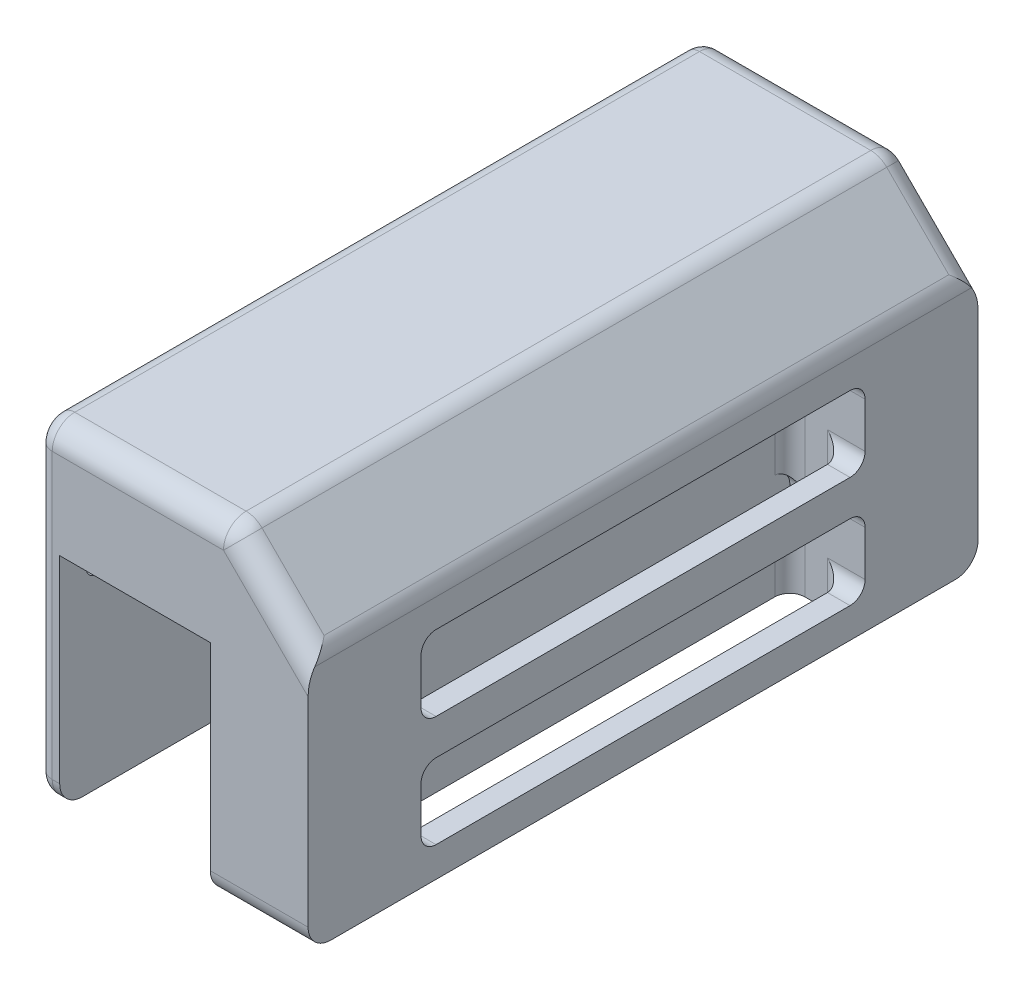
SolidWorks part; units mm, degrees
material "ABS"
ref_plane "Plano frontal" through (0, 0, 0) normal (0, 0, 1) x (1, 0, 0)
ref_plane "Plano superior" through (0, 0, 0) normal (0, 1, 0) x (1, 0, 0)
ref_plane "Plano direito" through (0, 0, 0) normal (1, 0, 0) x (0, 0, -1)
sketch "Esboço2" plane through (0, 0, 0) normal (1, 0, 0) x (0, 0, -1)
  line L1 (2.9016, -0.0625) -> (-35.0984, -0.0625) construction
  line L2 (2.9016, -0.0625) -> (-35.0984, -0.0625)
  line L6 (7.6893, -0.0625) -> (2.9016, -0.0625)
  line L8 (-39.8861, -0.0625) -> (-35.0984, -0.0625)
  line L9 (-60.5984, 9.4769) -> (-60.5984, 20.9769)
  line L10 (28.4016, 9.4769) -> (28.4016, 20.9769)
  line L11 (-57.5984, 23.9769) -> (25.4016, 23.9769)
  arc A0 (28.4016, 20.9769) -> (25.4016, 23.9769) centre (25.4016, 20.9769) ccw
  arc A1 (-60.5984, 20.9769) -> (-57.5984, 23.9769) centre (-57.5984, 20.9769) cw
  arc A2 (28.4016, 9.4769) -> (24.5016, 12.3387) centre (25.4016, 9.4769) ccw
  arc A3 (-48.8914, 5.5897) -> (-56.6984, 12.3387) centre (-60.5984, -0.0625) ccw
  arc A4 (-48.8914, 5.5897) -> (-39.8861, -0.0625) centre (-39.8861, 9.9375) ccw
  arc A5 (-60.5984, 9.4769) -> (-56.6984, 12.3387) centre (-57.5984, 9.4769) cw
  arc A6 (16.6946, 5.5897) -> (7.6893, -0.0625) centre (7.6893, 9.9375) cw
  arc A7 (16.6946, 5.5897) -> (24.5016, 12.3387) centre (28.4016, -0.0625) cw
  point P22 (28.4016, 12.9375)
  point P23 (-60.5984, 12.9375)
  dimension "D1" = 3
extrude "Ressalto-extrusão2" add sketch "Esboço2" along normal blind 30
sketch "Esboço3" plane through (0, 0, 0) normal (-1, 0, 0) x (0, 0, 1)
  line L0 (60.5984, 15.2269) -> (60.5984, 20.9769)
  line L1 (60.5984, 20.9769) -> (60.5984, 9.4769) construction
  line L2 (-28.4016, 15.2269) -> (-28.4016, 20.9769)
  line L3 (-28.4016, 9.4769) -> (-28.4016, 20.9769) construction
  line L4 (16.0984, 23.9769) -> (57.5984, 23.9769)
  line L5 (-25.4016, 23.9769) -> (57.5984, 23.9769) construction
  line L6 (16.0984, 23.9769) -> (-25.4016, 23.9769)
  line L7 (60.5984, 15.2269) -> (60.5984, -16.7731)
  line L8 (-28.4016, 15.2269) -> (-28.4016, -16.7731)
  line L9 (57.5984, -19.7731) -> (-25.4016, -19.7731)
  arc A0 (57.5984, 23.9769) -> (60.5984, 20.9769) centre (57.5984, 20.9769) cw
  arc A1 (-28.4016, 20.9769) -> (-25.4016, 23.9769) centre (-25.4016, 20.9769) cw
  arc A2 (-28.4016, -16.7731) -> (-25.4016, -19.7731) centre (-25.4016, -16.7731) ccw
  arc A3 (60.5984, -16.7731) -> (57.5984, -19.7731) centre (57.5984, -16.7731) cw
  dimension "D1" = 3
  dimension "D2" = 3
extrude "Ressalto-extrusão3" add sketch "Esboço3" along normal blind 3
sketch "Esboço4" plane through (30, 0, 0) normal (1, 0, 0) x (0, 0, -1)
  line L0 (-16.0984, 23.9769) -> (25.4016, 23.9769)
  line L1 (25.4016, 23.9769) -> (-57.5984, 23.9769) construction
  line L2 (-16.0984, 23.9769) -> (-57.5984, 23.9769)
  line L3 (28.4016, 15.2269) -> (28.4016, 20.9769)
  line L4 (28.4016, 9.4769) -> (28.4016, 20.9769) construction
  line L5 (-60.5984, 20.9769) -> (-60.5984, 15.2269)
  line L7 (28.4016, 15.2269) -> (28.4016, -16.7731)
  line L8 (28.4016, 9.4769) -> (28.4016, -16.7731) construction
  line L9 (-60.5984, 20.9769) -> (-60.5984, 9.4769) construction
  line L10 (-60.5984, 15.2269) -> (-60.5984, -16.7731)
  line L11 (25.4016, -19.7731) -> (-57.5984, -19.7731)
  arc A0 (25.4016, 23.9769) -> (28.4016, 20.9769) centre (25.4016, 20.9769) cw
  arc A1 (-60.5984, 20.9769) -> (-57.5984, 23.9769) centre (-57.5984, 20.9769) cw
  arc A2 (-60.5984, -16.7731) -> (-57.5984, -19.7731) centre (-57.5984, -16.7731) ccw
  arc A3 (28.4016, -16.7731) -> (25.4016, -19.7731) centre (25.4016, -16.7731) cw
  point P23 (28.4016, -19.7731)
  dimension "D1" = 3
extrude "Ressalto-extrusão4" add sketch "Esboço4" along normal blind 3 and the other way blind 10
sketch "Esboço8" plane through (33, 0, 0) normal (1, 0, 0) x (0, 0, -1)
  line L0 (-60.5984, 20.9769) -> (-60.5984, -16.7731) construction
  line L1 (-43.5984, 8.9769) -> (11.4016, 8.9769)
  line L2 (-45.5984, 6.9769) -> (-45.5984, 0.9769)
  line L3 (-43.5984, -1.0231) -> (11.4016, -1.0231)
  line L4 (13.4016, 6.9769) -> (13.4016, 0.9769)
  line L5 (28.4016, -16.7731) -> (28.4016, 20.9769) construction
  line L6 (25.4016, 23.9769) -> (-57.5984, 23.9769) construction
  line L7 (-57.5984, -19.7731) -> (25.4016, -19.7731) construction
  line L8 (-43.5984, -5.7731) -> (11.4016, -5.7731)
  line L9 (-45.5984, -7.7731) -> (-45.5984, -13.7731)
  line L10 (-43.5984, -15.7731) -> (11.4016, -15.7731)
  line L11 (13.4016, -7.7731) -> (13.4016, -13.7731)
  arc A0 (-43.5984, 8.9769) -> (-45.5984, 6.9769) centre (-43.5984, 6.9769) ccw
  arc A1 (-45.5984, 0.9769) -> (-43.5984, -1.0231) centre (-43.5984, 0.9769) ccw
  arc A2 (11.4016, 8.9769) -> (13.4016, 6.9769) centre (11.4016, 6.9769) cw
  arc A3 (11.4016, -1.0231) -> (13.4016, 0.9769) centre (11.4016, 0.9769) ccw
  arc A4 (11.4016, -5.7731) -> (13.4016, -7.7731) centre (11.4016, -7.7731) cw
  arc A5 (11.4016, -15.7731) -> (13.4016, -13.7731) centre (11.4016, -13.7731) ccw
  arc A6 (-45.5984, -13.7731) -> (-43.5984, -15.7731) centre (-43.5984, -13.7731) ccw
  arc A7 (-43.5984, -5.7731) -> (-45.5984, -7.7731) centre (-43.5984, -7.7731) ccw
  arc A8 (11.4016, -5.7731) -> (13.4016, -7.7731) centre (11.4016, -7.7731) cw
  point P22 (13.4016, 8.9769)
  point P25 (13.4016, -1.0231)
  point P28 (13.4016, -5.7731)
  point P31 (13.4016, -15.7731)
  dimension "D9" = 2
  dimension "D10" = 2
  dimension "D1" = 15
  dimension "D2" = 15
  dimension "D3" = 15
  dimension "D4" = 10
  dimension "D5" = 15
  dimension "D6" = 15
  dimension "D7" = 4
  dimension "D8" = 10
extrude "Corte-extrusão1" cut sketch "Esboço8" against normal blind 10 contours L8 A7 L9 A6 L10 A5 L11 A4 | L3 A3 L4 A2 L1 A0 L2 A1 region at (33, 3.9769, 16.0984) region at (33, -10.7731, 16.0984)
sketch "Esboço9" plane through (0, -19.7731, 0) normal (0, -1, 0) x (-1, 0, 0)
  line L0 (-20, 28.4016) -> (-33, 28.4016) construction
  line L1 (-25, 13.4016) -> (-28, 13.4016)
  line L2 (-23, 11.4016) -> (-23, -43.5984)
  line L3 (-25, -45.5984) -> (-28, -45.5984)
  line L4 (-30, 11.4016) -> (-30, -43.5984)
  line L5 (-20, -60.5984) -> (-33, -60.5984) construction
  line L6 (-33, -57.5984) -> (-33, 25.4016) construction
  line L7 (-20, -57.5984) -> (-20, 25.4016) construction
  arc A0 (-28, -45.5984) -> (-30, -43.5984) centre (-28, -43.5984) cw
  arc A1 (-23, -43.5984) -> (-25, -45.5984) centre (-25, -43.5984) cw
  arc A2 (-28, 13.4016) -> (-30, 11.4016) centre (-28, 11.4016) ccw
  arc A3 (-25, 13.4016) -> (-23, 11.4016) centre (-25, 11.4016) cw
  dimension "D5" = 2
  dimension "D1" = 15
  dimension "D2" = 15
  dimension "D3" = 3
  dimension "D4" = 3
extrude "Corte-extrusão2" cut sketch "Esboço9" against normal up to surface (28.75 mm away) up to face at (28, 8.9769, 16.0984)
sketch "Esboço10" plane through (0, 0, 0) normal (1, 0, 0) x (0, 0, -1)
  line L0 (-60.5984, -16.7731) -> (-60.5984, 9.4769) construction
  line L1 (28.4016, 9.4769) -> (28.4016, -16.7731) construction
  line L2 (-39.8861, -0.0625) -> (7.6893, -0.0625) construction
  circle A0 centre (-55.5984, 6.3387) radius 1.5
  circle A1 centre (23.4016, 6.3387) radius 1.5
  circle A2 centre (-16.0984, -8.5625) radius 1.5
  dimension "D1" = 3
  dimension "D2" = 3
  dimension "D3" = 3
  dimension "D4" = 5
  dimension "D5" = 6
  dimension "D6" = 5
  dimension "D7" = 6
  dimension "D8" = 8.5
  dimension "D9" = 44.5
extrude "Corte-extrusão3" cut sketch "Esboço10" against normal blind 10
sketch "Esboço12" plane through (0, 0, 0) normal (1, 0, 0) x (0, 0, -1)
  line L0 (28.4016, 9.4769) -> (28.4016, -16.7731) construction
  line L1 (-31.5984, -2.8625) -> (-25.5984, -2.8625)
  line L2 (-33.5984, -4.8625) -> (-33.5984, -14.7731)
  line L3 (-31.5984, -16.7731) -> (-25.5984, -16.7731)
  line L4 (-23.5984, -4.8625) -> (-23.5984, -14.7731)
  line L5 (-6.5984, -2.8625) -> (-0.5984, -2.8625)
  line L6 (-8.5984, -4.8625) -> (-8.5984, -14.7731)
  line L7 (-6.5984, -16.7731) -> (-0.5984, -16.7731)
  line L8 (1.4016, -4.8625) -> (1.4016, -14.7731)
  line L9 (-60.5984, -16.7731) -> (-60.5984, 9.4769) construction
  line L10 (25.4016, -19.7731) -> (-57.5984, -19.7731) construction
  line L11 (-39.8861, -0.0625) -> (7.6893, -0.0625) construction
  arc A0 (-0.5984, -2.8625) -> (1.4016, -4.8625) centre (-0.5984, -4.8625) cw
  arc A1 (-0.5984, -16.7731) -> (1.4016, -14.7731) centre (-0.5984, -14.7731) ccw
  arc A2 (-8.5984, -14.7731) -> (-6.5984, -16.7731) centre (-6.5984, -14.7731) ccw
  arc A3 (-6.5984, -2.8625) -> (-8.5984, -4.8625) centre (-6.5984, -4.8625) ccw
  arc A4 (-25.5984, -2.8625) -> (-23.5984, -4.8625) centre (-25.5984, -4.8625) cw
  arc A5 (-25.5984, -16.7731) -> (-23.5984, -14.7731) centre (-25.5984, -14.7731) ccw
  arc A6 (-31.5984, -2.8625) -> (-33.5984, -4.8625) centre (-31.5984, -4.8625) ccw
  arc A7 (-33.5984, -14.7731) -> (-31.5984, -16.7731) centre (-31.5984, -14.7731) ccw
  point P12 (-60.5984, -3.6481)
  point P21 (1.4016, -16.7731)
  point P24 (-8.5984, -16.7731)
  point P31 (-23.5984, -16.7731)
  point P36 (-33.5984, -16.7731)
  dimension "D9" = 2
  dimension "D1" = 52
  dimension "D2" = 52
  dimension "D3" = 3
  dimension "D4" = 3
  dimension "D5" = 2.8
  dimension "D6" = 2.8
  dimension "D7" = 10
  dimension "D8" = 10
extrude "Corte-extrusão4" cut sketch "Esboço12" against normal blind 10
fillet "Filete2" radius 2 8 edges at (-3, 23.0982, 59.7197) (-3, 2.1019, 60.5984) (-3, -18.8944, 59.7197) (-3, -19.7731, 16.0984) (-3, -18.8944, -27.5229) (-3, 2.1019, -28.4016) (-3, 23.0982, -27.5229) (-3, 23.9769, 16.0984)
sketch "Esboço13" plane through (-3, 0, 0) normal (-1, 0, 0) x (0, 0, 1)
  line L0 (57.5984, 21.9769) -> (-25.4016, 21.9769) construction
  line L2 (-26.4016, 20.9769) -> (-26.4016, -16.7731) construction
  circle A0 centre (27.4484, 3.9769) radius 1.5
  circle A1 centre (4.7484, 3.9769) radius 1.5
  point P10 (-26.4016, 2.1019)
  dimension "D1" = 22.7
  dimension "D2" = 3
  dimension "D3" = 3
  dimension "D4" = 18
  dimension "D5" = 31.15
extrude "Corte-extrusão5" cut sketch "Esboço13" against normal blind 16
ref_plane "Plano1" through (0, 0, -38.4016) normal (0, 0, -1) x (-1, 0, 0)
sketch "Esboço16" plane through (0, 0, -38.4016) normal (0, 0, -1) x (-1, 0, 0)
  line L0 (-23, 23.9769) -> (-33, 13.9769)
  line L1 (-33, 23.9769) -> (-23, 23.9769)
  line L2 (-33, 23.9769) -> (-33, 13.9769)
extrude "Corte-extrusão11" cut sketch "Esboço16" against normal blind 117 contours L0 L2 L1
fillet "Filete7" radius 3 6 edges at (29.5, 17.4769, 60.5984) (23.8787, 23.0982, 59.7197) (29.5, 17.4769, -28.4016) (23.8787, 23.0982, -27.5229) (33, 13.9769, 16.0984) (23, 23.9769, 16.0984)
